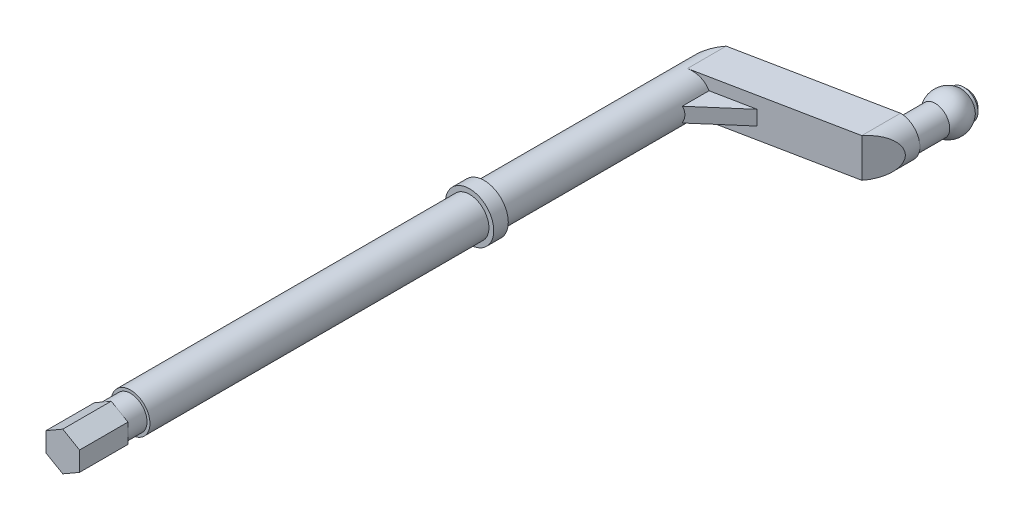
SolidWorks part; units mm, degrees
ref_plane "前视基准面" through (0, 0, 0) normal (0, 0, 1) x (1, 0, 0)
ref_plane "上视基准面" through (0, 0, 0) normal (0, 1, 0) x (1, 0, 0)
ref_plane "右视基准面" through (0, 0, 0) normal (1, 0, 0) x (0, 0, -1)
sketch "草图1" plane through (0, 0, 0) normal (0, 0, 1) x (1, 0, 0)
  circle A0 centre (0, 0) radius 2
  dimension "D1" = 4
extrude "凸台-拉伸1" add sketch "草图1" along normal blind 61.5
sketch "草图2" plane through (0, 0, 61.5) normal (0, 0, 1) x (1, 0, 0)
  circle A0 centre (0, 0) radius 2.5
  dimension "D1" = 5
extrude "凸台-拉伸2" add sketch "草图2" against normal blind 1.5 from offset 35 offset against normal yes
sketch "草图3" plane through (0, 0, 61.5) normal (0, 0, 1) x (1, 0, 0)
  circle A0 centre (0, 0) radius 1.7
  dimension "D1" = 3.4
extrude "凸台-拉伸3" add sketch "草图3" along normal blind 2
sketch "草图4" plane through (0, 0, 63.5) normal (0, 0, 1) x (1, 0, 0)
  line L1 (0, 2) -> (-1.7321, 1)
  line L2 (-1.7321, 1) -> (-1.7321, -1)
  line L3 (-1.7321, -1) -> (0, -2)
  line L4 (0, -2) -> (1.7321, -1)
  line L5 (1.7321, -1) -> (1.7321, 1)
  line L6 (1.7321, 1) -> (0, 2)
  circle A0 centre (0, 0) radius 1.7321 construction
  dimension "D1" = 2
extrude "凸台-拉伸4" add sketch "草图4" along normal blind 5
ref_plane "基准面1" through (0, 0, 1) normal (0, 0, -1) x (-1, 0, 0)
sketch "草图5" plane through (0, 0, 1) normal (0, 0, -1) x (-1, 0, 0)
  line L0 (0, 0) -> (-15, 0) construction
  circle A0 centre (-15, 0) radius 2
  dimension "D2" = 4
  dimension "D1" = 15
extrude "凸台-拉伸5" add sketch "草图5" along normal blind 4 separate body
sketch "草图6" plane through (0, 0, 0) normal (0, 1, 0) x (1, 0, 0)
  line L0 (0, 0) -> (15, 3)
  line L1 (17, 3) -> (13, 3) construction
  line L2 (15, 3) -> (15, -1)
  line L3 (13, -1) -> (17, -1) construction
  line L4 (15, -1) -> (0, -4)
  line L5 (0, -4) -> (0, 0)
extrude "凸台-拉伸6" add sketch "草图6" along normal blind 2 and the other way blind 2
sketch "草图7" plane through (0, 2, 0) normal (0, 1, 0) x (1, 0, 0)
  line L0 (0, 0) -> (-2, 0)
  line L1 (-2, 0) -> (-2, -2.5)
  line L2 (-2, 0) -> (-2, -25) construction
  line L3 (-2, -2.5) -> (0, 0)
  line L4 (15, -1) -> (17, 1.5)
  line L5 (17, -1) -> (17, 3) construction
  line L6 (17, 1.5) -> (17, -1)
  line L7 (17, -1) -> (15, -1)
  line L8 (15, 3) -> (13, 2.6)
  line L9 (13, 2.6) -> (13, 3)
  line L10 (13, 3) -> (15, 3)
  dimension "D1" = 2.5
  dimension "D2" = 2.5
extrude "切除-拉伸1" cut sketch "草图7" against normal up to next
sketch "草图8" plane through (0, 0, -3) normal (0, 0, -1) x (-1, 0, 0)
  line L0 (-17, 0) -> (-15.4, 0) construction
  arc A0 (-15, 2) -> (-15, -2) centre (-15, 0) ccw construction
  circle A1 centre (-15.4, 0) radius 1.5
  dimension "D1" = 3
  dimension "D2" = 1.6
extrude "凸台-拉伸7" add sketch "草图8" along normal blind 6.5 and the other way up to next
sketch "草图9" plane through (0, 0, 0) normal (0, 1, 0) x (1, 0, 0)
  line L0 (15.4, 9.5) -> (15.4, 7.5)
  line L1 (16.9, 9.5) -> (13.9, 9.5) construction
  line L2 (15.4, 7.5) -> (15.4, 5.5)
  arc A0 (15.4, 5.5) -> (15.4, 9.5) centre (15.4, 7.5) ccw
  dimension "D1" = 2
revolve "旋转1" add sketch "草图9" angle 360 about L0
chamfer "倒角1" distance 0.4 angle 45 1 edges at (13.9, 0, -9.5)
sketch "草图10" plane through (0, 0, 0) normal (0, 1, 0) x (1, 0, 0)
  line L0 (0, -2) -> (0, -8)
  line L1 (0, 0) -> (0, -4) construction
  line L2 (0, -8) -> (6, -2.8)
  line L3 (0, -4) -> (15, -1) construction
  line L6 (6, -2.8) -> (8, -1.0667)
  line L7 (8, -1.0667) -> (0, -2)
  dimension "D1" = 6
  dimension "D2" = 6
  dimension "D3" = 180
  dimension "D4" = 2
extrude "凸台-拉伸8" add sketch "草图10" along normal blind 0.75 and the other way blind 0.75
